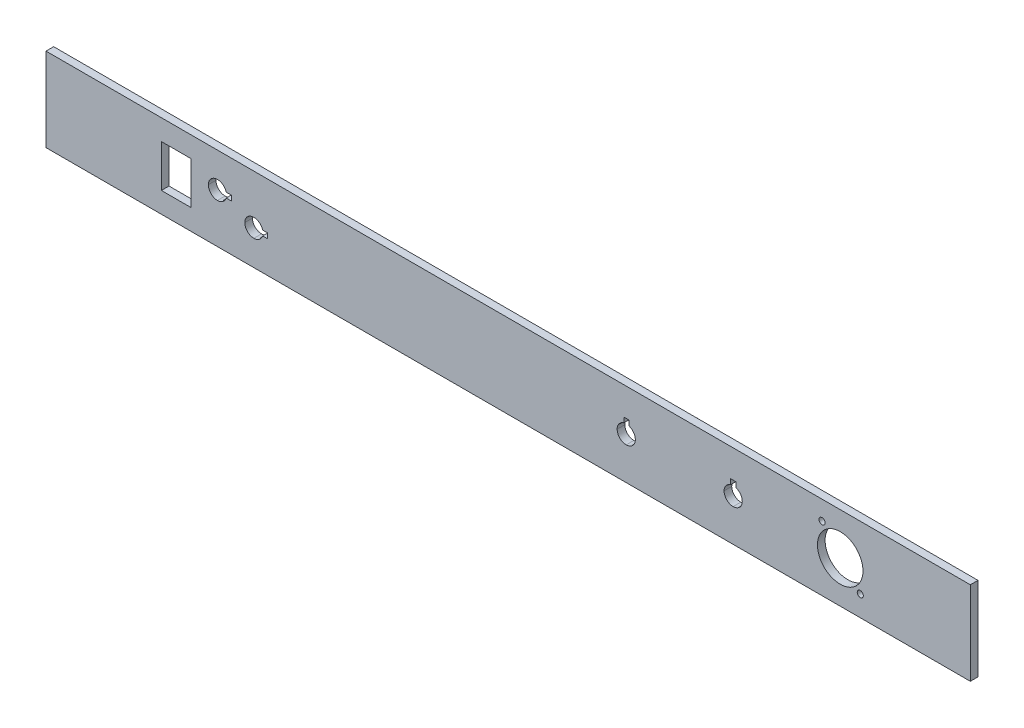
SolidWorks part; units mm, degrees
ref_plane "Front Plane" through (0, 0, 0) normal (0, 0, 1) x (1, 0, 0)
ref_plane "Top Plane" through (0, 0, 0) normal (0, 1, 0) x (1, 0, 0)
ref_plane "Right Plane" through (0, 0, 0) normal (1, 0, 0) x (0, 0, -1)
sketch "Sketch1" plane through (0, 0, 0) normal (0, 0, 1) x (1, 0, 0)
  line L1 (241.5, -21.85) -> (-241.5, -21.85)
  line L2 (241.5, -21.85) -> (241.5, 21.85)
  line L3 (241.5, 21.85) -> (-241.5, 21.85)
  line L4 (-241.5, -21.85) -> (-241.5, 21.85)
  line L5 (241.5, -21.85) -> (-241.5, 21.85) construction
  line L6 (241.5, 21.85) -> (-241.5, -21.85) construction
  point P0 (0, 0)
  dimension "D1" = 483
  dimension "D2" = 43.7
extrude "Boss-Extrude1" add sketch "Sketch1" along normal blind 4
sketch "Sketch2" plane through (0, 0, 4) normal (0, 0, 1) x (1, 0, 0)
  line L0 (-181.2079, -11.0681) -> (-181.2079, 11.0681)
  line L1 (-181.2079, 11.0681) -> (-165.7905, 11.0681)
  line L2 (-165.7905, 11.0681) -> (-165.7905, -11.0681)
  line L3 (-165.7905, -11.0681) -> (-181.2079, -11.0681)
  line L4 (-147.3683, 2.4325) -> (-144.689, 2.4325)
  line L5 (-144.689, 2.4325) -> (-144.689, 5.0746)
  line L6 (-144.689, 5.0746) -> (-147.3404, 5.0746)
  line L7 (-128.3216, -5.1862) -> (-125.6423, -5.1862)
  line L8 (-125.6423, -5.1862) -> (-125.6423, -2.5441)
  line L9 (-125.6423, -2.5441) -> (-128.2937, -2.5441)
  line L10 (-125.6423, -5.1862) -> (-125.6423, -11.0681) construction
  line L11 (-125.6423, -11.0681) -> (-181.2079, -11.0681) construction
  line L12 (-241.5, 0) -> (241.5, 0) construction
  line L13 (-241.5, 21.85) -> (-241.5, -21.85) construction
  line L14 (241.5, -21.85) -> (241.5, 21.85) construction
  line L15 (-181.2079, 0) -> (-164.5528, 0) construction
  line L16 (173.5, 11.9) -> (173.5, -11.9) construction
  line L17 (-203.5, 21.85) -> (-203.5, -21.85) construction
  line L18 (241.5, 21.85) -> (-241.5, 21.85) construction
  line L19 (-241.5, -21.85) -> (241.5, -21.85) construction
  line L20 (0, 0) -> (0, 21.85) construction
  line L21 (-151.9175, 8.5539) -> (-151.9175, -0.9445) construction
  line L22 (0, 0) -> (0, 21.85) construction
  line L23 (173.5, 11.9) -> (183.0068, 11.9) construction
  line L24 (163.0068, -13.5) -> (173.5, -13.5) construction
  line L25 (203.5, 21.85) -> (203.5, -21.85) construction
  line L26 (173.5, -13.5) -> (173.5, -11.9) construction
  line L27 (118.941, 7.2285) -> (116.299, 7.2285)
  line L28 (116.299, 7.2285) -> (116.299, 4.5771)
  line L29 (118.941, 4.5492) -> (118.941, 7.2285)
  line L30 (117.62, 7.2285) -> (117.62, -4.9318) construction
  line L31 (63.061, 7.2285) -> (60.419, 7.2285)
  line L32 (63.061, 4.5492) -> (63.061, 7.2285)
  line L33 (60.419, 7.2285) -> (60.419, 4.5771)
  line L34 (61.74, 7.2285) -> (61.74, -4.9318) construction
  line L35 (-173.4992, 11.0681) -> (-173.4992, 0) construction
  circle A0 centre (173.5, 0) radius 11.9
  circle A3 centre (183.9932, -11.1) radius 1.6
  circle A4 centre (163.9932, 11.9) radius 1.6
  spline S0 degree 3 poles (-156.6621, 3.8093) (-156.6621, 1.1878) (-154.5391, -0.9445) (-151.9175, -0.9445) knots 0 0 0 0 1 1 1 1
  spline S1 degree 3 poles (-151.9175, -0.9445) (-149.7741, -0.9445) (-147.9579, 0.4814) (-147.3683, 2.4325) knots 0 0 0 0 1 1 1 1
  spline S2 degree 3 poles (-147.3404, 5.0746) (-147.8969, 7.0777) (-149.7371, 8.5539) (-151.9175, 8.5539) knots 0 0 0 0 1 1 1 1
  spline S3 degree 3 poles (-151.9175, 8.5539) (-154.5391, 8.5539) (-156.6621, 6.4309) (-156.6621, 3.8093) knots 0 0 0 0 1 1 1 1
  spline S4 degree 3 poles (-137.6154, -3.8093) (-137.6154, -6.4309) (-135.4924, -8.5632) (-132.8708, -8.5632) knots 0 0 0 0 1 1 1 1
  spline S5 degree 3 poles (-132.8708, -8.5632) (-130.7274, -8.5632) (-128.9111, -7.1373) (-128.3216, -5.1862) knots 0 0 0 0 1 1 1 1
  spline S6 degree 3 poles (-128.2937, -2.5441) (-128.8502, -0.541) (-130.6903, 0.9352) (-132.8708, 0.9352) knots 0 0 0 0 1 1 1 1
  spline S7 degree 3 poles (-132.8708, 0.9352) (-135.4924, 0.9352) (-137.6154, -1.1878) (-137.6154, -3.8093) knots 0 0 0 0 1 1 1 1
  spline S8 degree 3 poles (112.8196, 0) (112.8196, -2.6216) (114.9426, -4.7446) (117.5642, -4.7446) knots 0 0 0 0 1 1 1 1
  spline S9 degree 3 poles (122.3181, 0) (122.3181, 2.1434) (120.8921, 3.9597) (118.941, 4.5492) knots 0 0 0 0 1 1 1 1
  spline S10 degree 3 poles (116.299, 4.5771) (114.2958, 4.0206) (112.8196, 2.1805) (112.8196, 0) knots 0 0 0 0 1 1 1 1
  spline S11 degree 3 poles (117.5642, -4.7446) (120.1858, -4.7446) (122.3181, -2.6216) (122.3181, 0) knots 0 0 0 0 1 1 1 1
  spline S12 degree 3 poles (61.6842, -4.7446) (64.3058, -4.7446) (66.4381, -2.6216) (66.4381, 0) knots 0 0 0 0 1 1 1 1
  spline S13 degree 3 poles (56.9396, 0) (56.9396, -2.6216) (59.0626, -4.7446) (61.6842, -4.7446) knots 0 0 0 0 1 1 1 1
  spline S14 degree 3 poles (66.4381, 0) (66.4381, 2.1434) (65.0121, 3.9597) (63.061, 4.5492) knots 0 0 0 0 1 1 1 1
  spline S15 degree 3 poles (60.419, 4.5771) (58.4158, 4.0206) (56.9396, 2.1805) (56.9396, 0) knots 0 0 0 0 1 1 1 1
  dimension "D10" = 23
  dimension "D1" = 38
  dimension "D2" = 55.88
  dimension "D3" = 19.0467
  dimension "D4" = 48.3371
  dimension "D5" = 9.3217
  dimension "D6" = 2.6421
  dimension "D7" = 2.6793
  dimension "D8" = 9.4985
  dimension "D9" = 30
extrude "Cut-Extrude1" cut sketch "Sketch2" against normal blind 4
